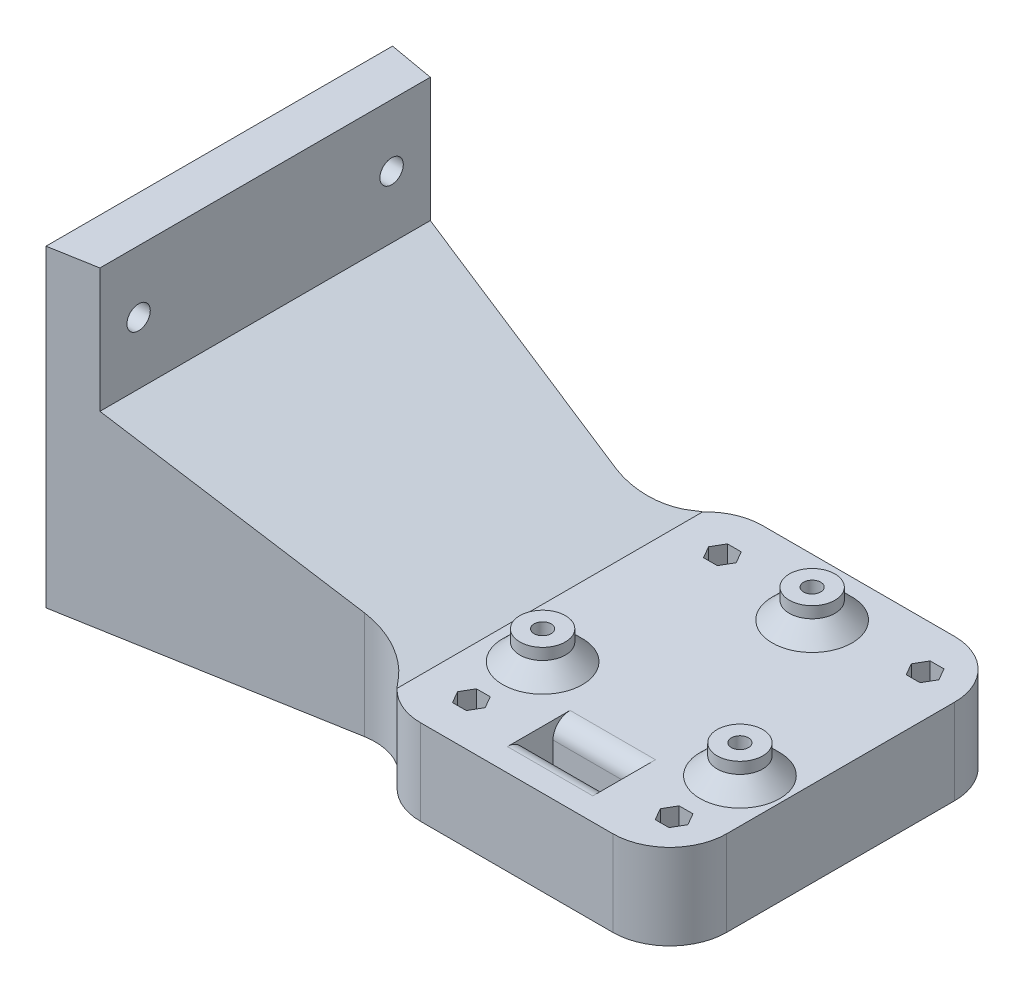
SolidWorks part; units mm, degrees
ref_plane "前视基准面" through (0, 0, 0) normal (0, 0, 1) x (1, 0, 0)
ref_plane "上视基准面" through (0, 0, 0) normal (0, 1, 0) x (1, 0, 0)
ref_plane "右视基准面" through (0, 0, 0) normal (1, 0, 0) x (0, 0, -1)
sketch "草图1" plane through (0, 0, 0) normal (0, 1, 0) x (1, 0, 0)
  line L0 (-25, 0) -> (25, 0) construction
  line L1 (-25, 30) -> (25, 30)
  line L2 (-25, 30) -> (-25, -30)
  line L3 (-25, -30) -> (25, -30)
  line L4 (25, 30) -> (25, -30)
  line L5 (-25, 30) -> (25, -30) construction
  line L6 (-25, -30) -> (25, 30) construction
  line L7 (0, 30) -> (0, -30) construction
  line L8 (0, 0) -> (-17.3205, -10) construction
  line L9 (0, 0) -> (0, 20) construction
  line L10 (0, 0) -> (17.3205, -10) construction
  circle A0 centre (-17.7955, 22.0345) radius 1
  circle A1 centre (17.7955, 22.0345) radius 1
  circle A2 centre (17.7955, -22.0345) radius 1
  circle A3 centre (-17.7955, -22.0345) radius 1
  circle A8 centre (0, 0) radius 20 construction
  circle A9 centre (-17.3205, -10) radius 1.5
  circle A10 centre (17.3205, -10) radius 1.5
  circle A11 centre (0, 20) radius 1.5
  point P0 (0, 0)
  dimension "D4" = 2
  dimension "D5" = 2
  dimension "D14" = 40
  dimension "D15" = 3
  dimension "D16" = 3
  dimension "D17" = 3
  dimension "D1" = 60
  dimension "D2" = 50
  dimension "D3" = 35.591
  dimension "D6" = 7.2045
  dimension "D7" = 7.9655
extrude "凸台-拉伸1" add sketch "草图1" along normal blind 5 and the other way blind 10
fillet "圆角1" radius 10 1 edges at (25, -2.5, -30)
sketch "草图5" plane through (0, 5, 0) normal (0, 1, 0) x (1, 0, 0)
  circle A1 centre (-17.3205, -10) radius 4
  circle A2 centre (17.3205, -10) radius 4
  circle A3 centre (0, 20) radius 4
  circle A4 centre (-17.3205, -10) radius 1.5
  circle A5 centre (17.3205, -10) radius 1.5
  circle A6 centre (0, 20) radius 1.5
  dimension "D1" = 8
  dimension "D2" = 8
  dimension "D3" = 8
extrude "凸台-拉伸3" add sketch "草图5" along normal blind 5
sketch "草图6" plane through (0, -10, 0) normal (0, -1, 0) x (1, 0, 0)
  circle A0 centre (-17.3205, 10) radius 3.5
  circle A1 centre (17.3205, 10) radius 3.5
  circle A2 centre (0, -20) radius 3.5
  dimension "D1" = 7
  dimension "D2" = 7
  dimension "D3" = 7
extrude "切除-拉伸1" cut sketch "草图6" against normal blind 6
sketch "草图7" plane through (0, 5, 0) normal (0, 1, 0) x (1, 0, 0)
  line L0 (0, 0) -> (0, -30) construction
  line L1 (-25, -30) -> (25, -30) construction
  line L3 (0, 0) -> (0, -18) construction
  line L4 (-7.5, -18) -> (7.5, -18)
  line L5 (-7.5, -18) -> (-7.5, -23)
  line L6 (-7.5, -23) -> (7.5, -23)
  line L7 (7.5, -18) -> (7.5, -23)
  line L8 (-7.5, -18) -> (7.5, -23) construction
  line L9 (-7.5, -23) -> (7.5, -18) construction
  point P9 (0, -20.5)
  dimension "D1" = 5
  dimension "D2" = 15
  dimension "D3" = 18
extrude "切除-拉伸2" cut sketch "草图7" against normal through all
sketch "草图9" plane through (0, 5, 0) normal (0, 1, 0) x (1, 0, 0)
  line L1 (-15.3706, 22.0345) -> (-16.5831, 24.1345)
  line L2 (-16.5831, 24.1345) -> (-19.0079, 24.1345)
  line L3 (-19.0079, 24.1345) -> (-20.2204, 22.0345)
  line L4 (-20.2204, 22.0345) -> (-19.0079, 19.9345)
  line L5 (-19.0079, 19.9345) -> (-16.5831, 19.9345)
  line L6 (-16.5831, 19.9345) -> (-15.3706, 22.0345)
  line L7 (20.2204, 22.0345) -> (19.0079, 24.1345)
  line L8 (19.0079, 24.1345) -> (16.5831, 24.1345)
  line L9 (16.5831, 24.1345) -> (15.3706, 22.0345)
  line L10 (15.3706, 22.0345) -> (16.5831, 19.9345)
  line L11 (16.5831, 19.9345) -> (19.0079, 19.9345)
  line L12 (19.0079, 19.9345) -> (20.2204, 22.0345)
  line L13 (20.2204, -22.0345) -> (19.0079, -19.9345)
  line L14 (19.0079, -19.9345) -> (16.5831, -19.9345)
  line L15 (16.5831, -19.9345) -> (15.3706, -22.0345)
  line L16 (15.3706, -22.0345) -> (16.5831, -24.1345)
  line L17 (16.5831, -24.1345) -> (19.0079, -24.1345)
  line L18 (19.0079, -24.1345) -> (20.2204, -22.0345)
  line L19 (-15.3706, -22.0345) -> (-16.5831, -19.9345)
  line L20 (-16.5831, -19.9345) -> (-19.0079, -19.9345)
  line L21 (-19.0079, -19.9345) -> (-20.2204, -22.0345)
  line L22 (-20.2204, -22.0345) -> (-19.0079, -24.1345)
  line L23 (-19.0079, -24.1345) -> (-16.5831, -24.1345)
  line L24 (-16.5831, -24.1345) -> (-15.3706, -22.0345)
  circle A0 centre (-17.7955, 22.0345) radius 2.1 construction
  circle A1 centre (17.7955, 22.0345) radius 2.1 construction
  circle A2 centre (17.7955, -22.0345) radius 2.1 construction
  circle A3 centre (-17.7955, -22.0345) radius 2.1 construction
  point P28 (-17.7955, -19.9345)
  dimension "D1" = 4.2
  dimension "D2" = 4.2
  dimension "D3" = 4.2
  dimension "D4" = 4.2
extrude "切除-拉伸3" cut sketch "草图9" against normal blind 10
chamfer "倒角1" distance 3 angle 45 3 edges at (0, 5, -16) (17.3205, 5, 14) (-17.3205, 5, 14)
fillet "圆角5" radius 3 4 edges at (0, -10, 18) (0, -10, 23) (0, 5, 23) (0, 5, 18)
fillet "圆角6" radius 10 1 edges at (25, -2.5, 30)
sketch "草图13" plane through (0, 5, 0) normal (0, 1, 0) x (1, 0, 0)
  line L0 (-25, 20) -> (-84.0885, 30.4189)
  line L1 (-84.0885, 30.4189) -> (-84.0885, -30.4189)
  line L2 (-84.0885, -30.4189) -> (-25, -20)
  line L3 (-25, -20) -> (-25, 20)
  dimension "D1" = 100
  dimension "D2" = 100
  dimension "D3" = 60
  dimension "D4" = 60
extrude "凸台-拉伸7" add sketch "草图13" against normal up to surface (15 mm away) up to face at (0, -10, 20.5)
sketch "草图15" plane through (0, 5, 0) normal (0, 1, 0) x (1, 0, 0)
  line L0 (-84.0885, 30.4189) -> (-84.0885, -30.4189)
  line L1 (-84.0885, -30.4189) -> (-76.0415, -29)
  line L2 (-84.0885, -30.4189) -> (-25, -20) construction
  line L3 (-76.0415, -29) -> (-76.0415, 29)
  line L4 (-25, 20) -> (-84.0885, 30.4189) construction
  line L5 (-76.0415, 29) -> (-84.0885, 30.4189)
  dimension "D1" = 58
extrude "凸台-拉伸8" add sketch "草图15" along normal blind 40
chamfer "倒角2" distance 50 angle 20 1 edges at (-76.0415, 5, 0) first distance on face at (0, 5, -13)
sketch "草图16" plane through (-76.0415, 0, 0) normal (1, 0, 0) x (0, 0, -1)
  line L0 (-29, 45) -> (-15.4202, 23.1985) construction
  line L1 (-29, 23.1985) -> (29, 23.1985) construction
  line L2 (-29, 23.1985) -> (-15.4202, 45) construction
  line L3 (-29, 45) -> (29, 45) construction
  line L4 (0, 23.1985) -> (0, 45) construction
  circle A0 centre (-22.2101, 34.0993) radius 2.05
  circle A1 centre (22.2101, 34.0993) radius 2.05
  dimension "D1" = 4.1
extrude "切除-拉伸4" cut sketch "草图16" against normal blind 30
fillet "圆角7" radius 10 2 edges at (-25, -2.5, 20) (-25, -2.5, -20)
fillet "圆角8" radius 10 2 edges at (-25, -2.5, 30) (-25, -2.5, -30)
